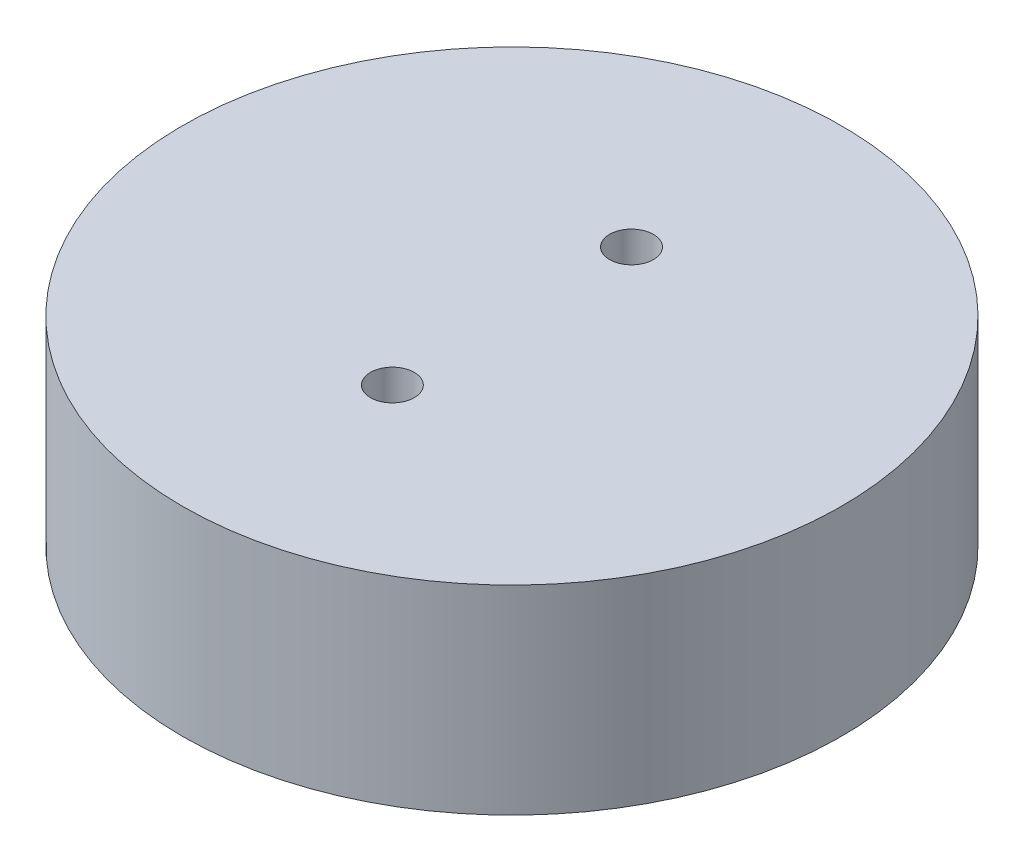
SolidWorks part; units mm, degrees
ref_plane "Front Plane" through (0, 0, 0) normal (0, 0, 1) x (1, 0, 0)
ref_plane "Top Plane" through (0, 0, 0) normal (0, 1, 0) x (1, 0, 0)
ref_plane "Right Plane" through (0, 0, 0) normal (1, 0, 0) x (0, 0, -1)
sketch "Sketch1" plane through (0, 0, 0) normal (0, 1, 0) x (1, 0, 0)
  circle A0 centre (0, 0) radius 41.35
extrude "Boss-Extrude1" add sketch "Sketch1" along normal blind 25
sketch "Sketch2" plane through (0, 25, 0) normal (0, 1, 0) x (1, 0, 0)
  circle A0 centre (0, 15) radius 2.75
  circle A1 centre (0, -15) radius 2.75
  dimension "D1" = 15
  dimension "D2" = 15
extrude "Cut-Extrude1" cut sketch "Sketch2" against normal blind 25
